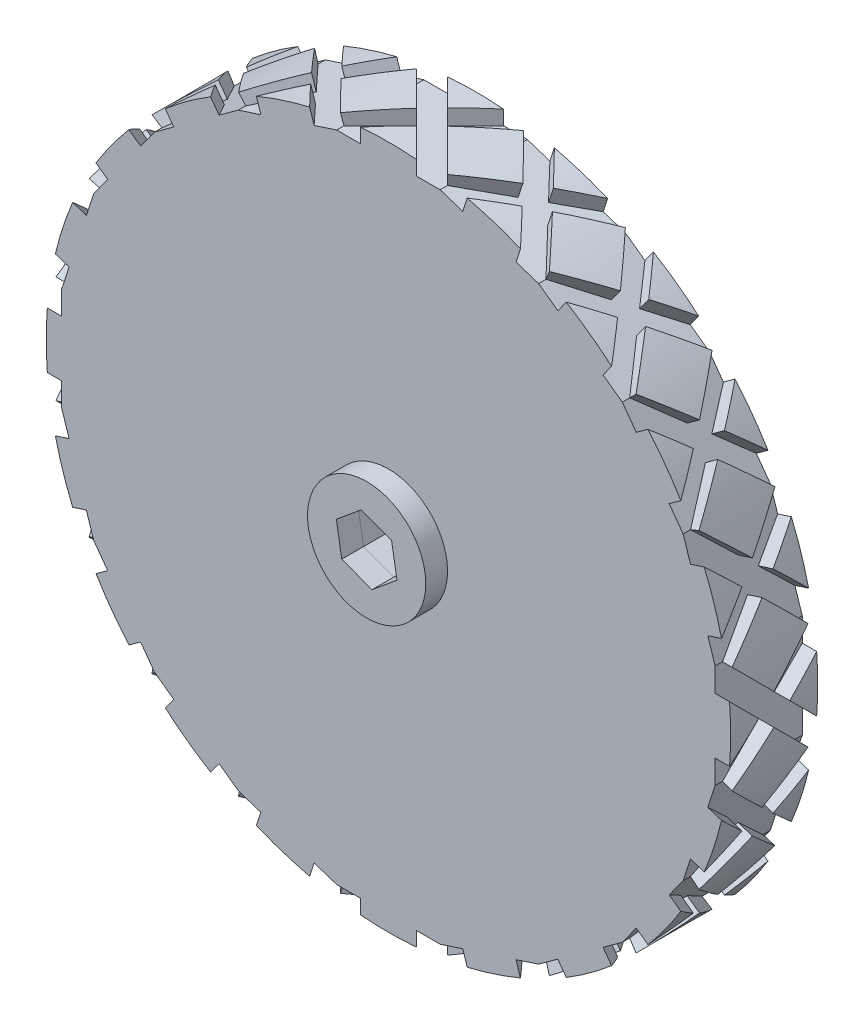
SolidWorks part; units mm, degrees
ref_plane "Front Plane" through (0, 0, 0) normal (0, 0, 1) x (1, 0, 0)
ref_plane "Top Plane" through (0, 0, 0) normal (0, 1, 0) x (1, 0, 0)
ref_plane "Right Plane" through (0, 0, 0) normal (1, 0, 0) x (0, 0, -1)
sketch "Sketch1" plane through (0, 0, 0) normal (0, 0, 1) x (1, 0, 0)
  line L6 (-0.1641, 3.0677) -> (-0.9201, 2.4418) construction
  line L7 (-0.1737, 3.1246) -> (0.1737, 1.0754) construction
  line L12 (0.9742, 1.7381) -> (0.8005, 2.7627)
  line L13 (0.8005, 2.7627) -> (-0.1737, 3.1246)
  line L14 (-0.1737, 3.1246) -> (-0.9742, 2.4619)
  line L15 (-0.9742, 2.4619) -> (-0.8005, 1.4373)
  line L16 (-0.8005, 1.4373) -> (0.1737, 1.0754)
  line L17 (0.1737, 1.0754) -> (0.9742, 1.7381)
  circle A0 centre (0, 2.1) radius 1.925 construction
  circle A1 centre (0, 2.1) radius 1.925 construction
  circle A2 centre (0, 2.1) radius 2.5
  dimension "D2" = 5
  dimension "D1" = 0.05
extrude "Boss-Extrude1" add sketch "Sketch1" along normal offset from surface (1.5 mm away) 0.1 offset beyond the face yes
sketch "Sketch2" plane through (0, 0, 1.5) normal (0, 0, 1) x (1, 0, 0)
  line L6 (0.1737, 1.0754) -> (0.9742, 1.7381)
  line L7 (-0.8005, 1.4373) -> (0.1737, 1.0754)
  line L8 (-0.9742, 2.4619) -> (-0.8005, 1.4373)
  line L9 (-0.1737, 3.1246) -> (-0.9742, 2.4619)
  line L10 (0.8005, 2.7627) -> (-0.1737, 3.1246)
  line L11 (0.9742, 1.7381) -> (0.8005, 2.7627)
  line L12 (0.1737, 1.0754) -> (0.9742, 1.7381)
  line L13 (-0.8005, 1.4373) -> (0.1737, 1.0754)
  line L14 (-0.9742, 2.4619) -> (-0.8005, 1.4373)
  line L15 (-0.1737, 3.1246) -> (-0.9742, 2.4619)
  line L16 (0.8005, 2.7627) -> (-0.1737, 3.1246)
  line L17 (0.9742, 1.7381) -> (0.8005, 2.7627)
  circle A0 centre (0, 2.1) radius 11
  circle A1 centre (0, 2.1) radius 2.5
  circle A2 centre (0, 2.1) radius 2.5 construction
  dimension "D3" = 22
  dimension "D1" = 0
  dimension "D2" = 0
extrude "Boss-Extrude2" add sketch "Sketch2" along normal blind 3
sketch "Sketch3" plane through (0, 0, 4.5) normal (0, 0, 1) x (1, 0, 0)
  line L7 (0.8005, 2.7627) -> (-0.1737, 3.1246)
  line L8 (0.9742, 1.7381) -> (0.8005, 2.7627)
  line L9 (0.1737, 1.0754) -> (0.9742, 1.7381)
  line L10 (-0.8005, 1.4373) -> (0.1737, 1.0754)
  line L11 (-0.9742, 2.4619) -> (-0.8005, 1.4373)
  line L12 (-0.1737, 3.1246) -> (-0.9742, 2.4619)
  line L13 (0.8005, 2.7627) -> (-0.1737, 3.1246)
  line L14 (0.9742, 1.7381) -> (0.8005, 2.7627)
  line L15 (0.1737, 1.0754) -> (0.9742, 1.7381)
  line L16 (-0.8005, 1.4373) -> (0.1737, 1.0754)
  line L17 (-0.9742, 2.4619) -> (-0.8005, 1.4373)
  line L18 (-0.1737, 3.1246) -> (-0.9742, 2.4619)
  circle A0 centre (0, 2.1) radius 1.0392 construction
  circle A1 centre (0, 2.1) radius 1.9
  dimension "D2" = 3.8
  dimension "D3" = 0.8608
  dimension "D1" = 0
extrude "Boss-Extrude3" add sketch "Sketch3" along normal blind 0.6
sketch "Sketch4" plane through (0, 0, 4.5) normal (0, 0, 1) x (1, 0, 0)
  circle A0 centre (0, 2.1) radius 1.9 construction
  circle A1 centre (0, 2.1) radius 11
  circle A2 centre (0, 2.1) radius 11
  circle A3 centre (0, 2.1) radius 1.9
  dimension "D1" = 0
extrude "Cut-Extrude1" cut sketch "Sketch4" against normal blind 0.1
sketch "Sketch5" plane through (0, 0, 1.5) normal (0, 0, -1) x (-1, 0, 0)
  circle A0 centre (0, 2.1) radius 2.5 construction
  circle A1 centre (0, 2.1) radius 11
  circle A2 centre (0, 2.1) radius 11
  circle A3 centre (0, 2.1) radius 2.5
  dimension "D1" = 0
extrude "Cut-Extrude2" cut sketch "Sketch5" against normal blind 0.1
ref_plane "Plane1" through (0, -10, 0) normal (0, 1, 0) x (1, 0, 0)
ref_plane "Plane2" through (0, 0, 3) normal (0, 0, -1) x (-1, 0, 0)
sketch "Sketch8" plane through (0, 0, 3) normal (0, 0, -1) x (-1, 0, 0)
  line L0 (0, 2.1) -> (0, -8.9) construction
  line L1 (-0.5, -9.4) -> (0.5, -9.4)
  line L2 (-0.5, -9.4) -> (-0.5, -8.4)
  line L3 (-0.5, -8.4) -> (0.5, -8.4)
  line L4 (0.5, -9.4) -> (0.5, -8.4)
  line L5 (-0.5, -9.4) -> (0.5, -8.4) construction
  line L6 (-0.5, -8.4) -> (0.5, -9.4) construction
  circle A0 centre (0, 2.1) radius 11 construction
  point P0 (0, -8.9)
  dimension "D1" = 1
  dimension "D2" = 1
sketch "Sketch9" plane through (0, -10, 0) normal (0, 1, 0) x (1, 0, 0)
  line L0 (0, -3) -> (3.304, 0.304)
  line L1 (0, -3) -> (-3.2004, -6.2004)
  line L2 (12.1, -3) -> (-12.1, -3) construction
  dimension "D1" = 45
sweep "Cut-Sweep1" cut profiles "Sketch8" path "Sketch9"
mirror "Mirror1" about plane through (0, 0, 0) normal (1, 0, 0) of "Cut-Sweep1"
pattern_circular "CirPattern2" count 20 over 360 about axis through (0, 2.1, 5.1) along (0, 0, 1) of "Cut-Sweep1", "Mirror1"
split "Split1" bodies to split 110 resulting bodies 111 112 split by face at (0, 2.1, 4.4)
sketch "Sketch10" plane through (0, 0, 4.4) normal (0, 0, 1) x (1, 0, 0)
  circle A0 centre (0, 2.1) radius 1.0392 construction
  circle A1 centre (0, 2.1) radius 9.5
  circle A2 centre (0, 2.1) radius 4
  dimension "D1" = 8
  dimension "D2" = 19
extrude "Cut-Extrude3" [suppressed] cut sketch "Sketch10" against normal blind 0.4
sketch "Sketch11" plane through (0, 0, 1.6) normal (0, 0, -1) x (-1, 0, 0)
  circle A1 centre (0, 2.1) radius 4
  circle A2 centre (0, 2.1) radius 4
  circle A3 centre (0, 2.1) radius 9.5
  circle A4 centre (0, 2.1) radius 9.5
  dimension "D1" = 0
  dimension "D2" = 0
extrude "Cut-Extrude4" cut sketch "Sketch11" against normal blind 0.4
